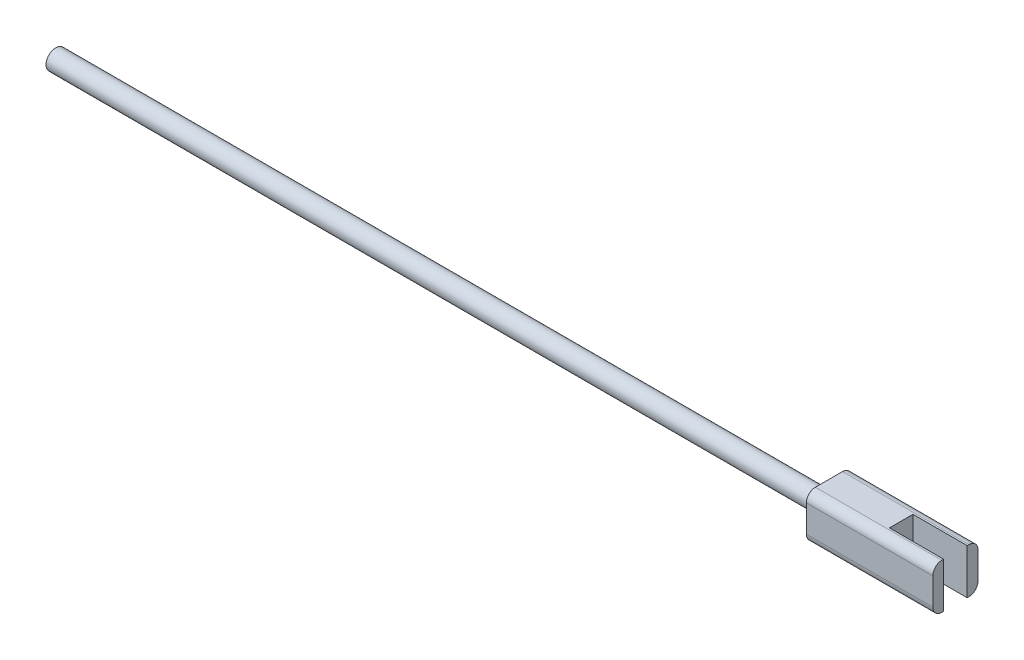
SolidWorks part; units mm, degrees
ref_plane "Front Plane" through (0, 0, 0) normal (0, 0, 1) x (1, 0, 0)
ref_plane "Top Plane" through (0, 0, 0) normal (0, 1, 0) x (1, 0, 0)
ref_plane "Right Plane" through (0, 0, 0) normal (1, 0, 0) x (0, 0, -1)
sketch "Sketch1" plane through (0, 0, 0) normal (1, 0, 0) x (0, 0, -1)
  circle A0 centre (0, 0) radius 1.09
extrude "Boss-Extrude1" add sketch "Sketch1" along normal blind 87.575
ref_plane "Plane1" through (85.575, 0, 0) normal (1, 0, 0) x (0, 0, -1)
sketch "Sketch2" plane through (85.575, 0, 0) normal (1, 0, 0) x (0, 0, -1)
  line L0 (-1.5, -2.5) -> (1.5, -2.5)
  line L1 (2.5, -1.5) -> (2.5, 1.5)
  line L2 (1.5, 2.5) -> (-1.5, 2.5)
  line L3 (-2.5, 1.5) -> (-2.5, -1.5)
  arc A0 (1.5, -2.5) -> (2.5, -1.5) centre (1.5, -1.5) ccw
  arc A1 (2.5, 1.5) -> (1.5, 2.5) centre (1.5, 1.5) ccw
  arc A2 (-1.5, 2.5) -> (-2.5, 1.5) centre (-1.5, 1.5) ccw
  arc A3 (-2.5, -1.5) -> (-1.5, -2.5) centre (-1.5, -1.5) ccw
extrude "Boss-Extrude2" add sketch "Sketch2" along normal blind 14
sketch "Sketch3" plane through (0, 0, 0) normal (0, 1, 0) x (1, 0, 0)
  line L0 (93.575, 1.3) -> (100.575, 1.3)
  line L1 (100.575, 1.3) -> (100.575, -1.3)
  line L2 (100.575, -1.3) -> (93.575, -1.3)
  line L3 (93.575, -1.3) -> (93.575, 1.3)
extrude "Cut-Extrude1" cut sketch "Sketch3" against normal through all and the other way through all
